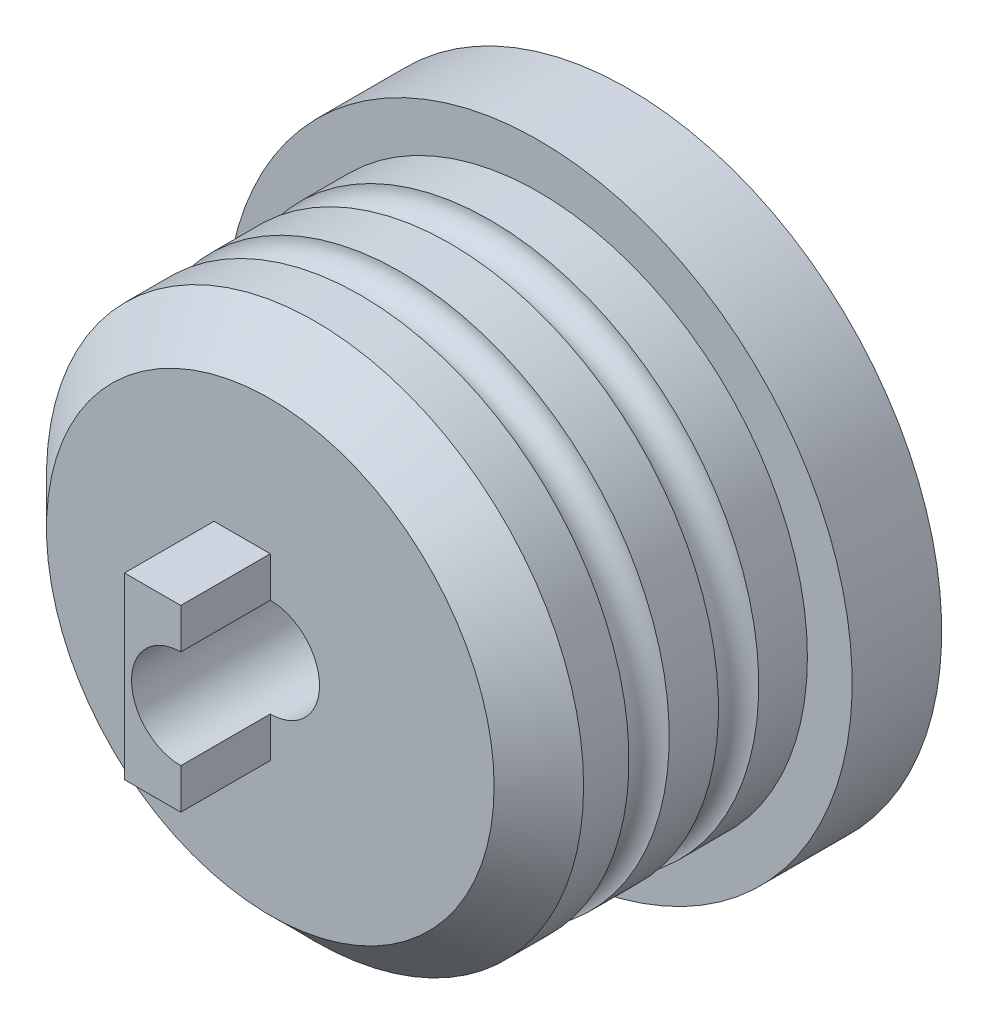
SolidWorks part; units mm, degrees
ref_plane "Plan de face" through (0, 0, 0) normal (0, 0, 1) x (1, 0, 0)
ref_plane "Plan de dessus" through (0, 0, 0) normal (0, 1, 0) x (1, 0, 0)
ref_plane "Plan de droite" through (0, 0, 0) normal (1, 0, 0) x (0, 0, -1)
sketch "Esquisse1" plane through (0, 0, 0) normal (0, 0, 1) x (1, 0, 0)
  circle A0 centre (0, 0) radius 30
extrude "Boss.-Extru.1" add sketch "Esquisse1" along normal blind 30
sketch "Esquisse2" plane through (0, 0, 0) normal (0, 0, -1) x (-1, 0, 0)
  circle A0 centre (0, 0) radius 35
extrude "Boss.-Extru.2" add sketch "Esquisse2" along normal blind 10
chamfer "Chanfrein1" distance 5 angle 45 1 edges at (30, 0, 30)
sketch "Esquisse3" plane through (0, 0, -10) normal (0, 0, -1) x (-1, 0, 0)
  circle A0 centre (0, 0) radius 5.5
extrude "Enlèv. mat.-Extru.1" cut sketch "Esquisse3" against normal up to surface (40 mm away) up to face at (25, 0, 30)
sketch "Esquisse4" plane through (0, 0, 30) normal (0, 0, 1) x (1, 0, 0)
  line L0 (0, 10) -> (0, 5.5)
  line L1 (0, 10) -> (-2.5, 10)
  line L3 (-2.5, -10) -> (0, -10)
  line L4 (0, -10) -> (0, -5.5)
  line L5 (-2.5, 10) -> (-3.5, 10)
  line L7 (-3.5, -10) -> (-2.5, -10)
  line L8 (-3.5, -10) -> (-6.2845, -10)
  line L9 (-6.2845, -10) -> (-6.2845, 10)
  line L10 (-6.2845, 10) -> (-3.5, 10)
  circle A0 centre (0, 0) radius 5.5 construction
  arc A1 (0, 5.5) -> (0, -5.5) centre (0, 0) ccw
extrude "Boss.-Extru.6" add sketch "Esquisse4" along normal blind 10
sketch "Esquisse5" plane through (0, 0, 0) normal (1, 0, 0) x (0, 0, -1)
  line L1 (-25, -30) -> (0, -30) construction
  circle A0 centre (-7.6875, -30) radius 2.25
  point P0 (-7.6875, -29.825)
ref_plane "Plan2" through (0, 0, 8) normal (0, 0, 1) x (1, 0, 0)
sketch "Esquisse6" plane through (0, 0, 8) normal (0, 0, 1) x (1, 0, 0)
  circle A0 centre (0, 0) radius 23.0016
sweep "Enlèvement de matière-Balayage1" cut profiles "Esquisse5" path "Esquisse6"
pattern_linear "Répétition linéaire1" count 2 spacing 10 along (0, 0, 1) of "Enlèvement de matière-Balayage1"
